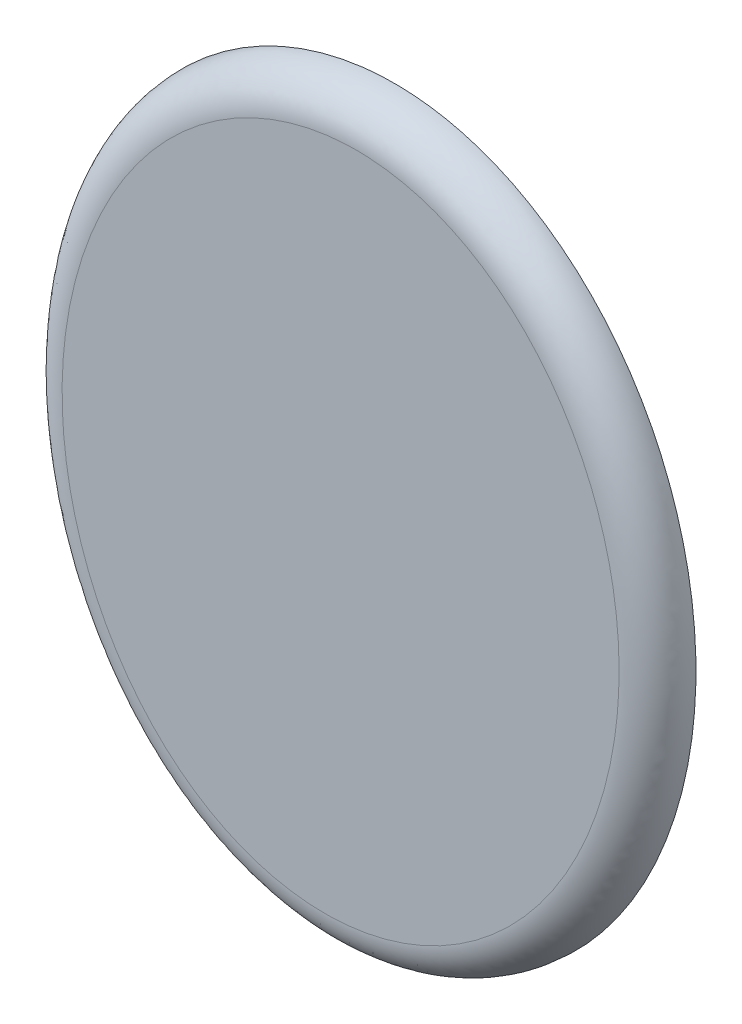
SolidWorks part; units mm, degrees
ref_plane "Front Plane" through (0, 0, 0) normal (0, 0, 1) x (1, 0, 0)
ref_plane "Top Plane" through (0, 0, 0) normal (0, 1, 0) x (1, 0, 0)
ref_plane "Right Plane" through (0, 0, 0) normal (1, 0, 0) x (0, 0, -1)
sketch "Sketch1" plane through (0, 0, 0) normal (0, 0, 1) x (1, 0, 0)
  ellipse E0 centre (0, 0) end of major axis (3.4252, 24.7422) minor radius 20.8592
  point P1 (-16.3933, 0)
  point P7 (13.0372, 0)
  point P9 (0.9716, 28.779)
  point P10 (20.6744, -2.7706)
  point P11 (3.4252, 24.7422)
extrude "Boss-Extrude1" add sketch "Sketch1" along normal blind 2.54
fillet "Fillet1" radius 2.54 1 edges at (3.4252, 24.7422, 2.54)
